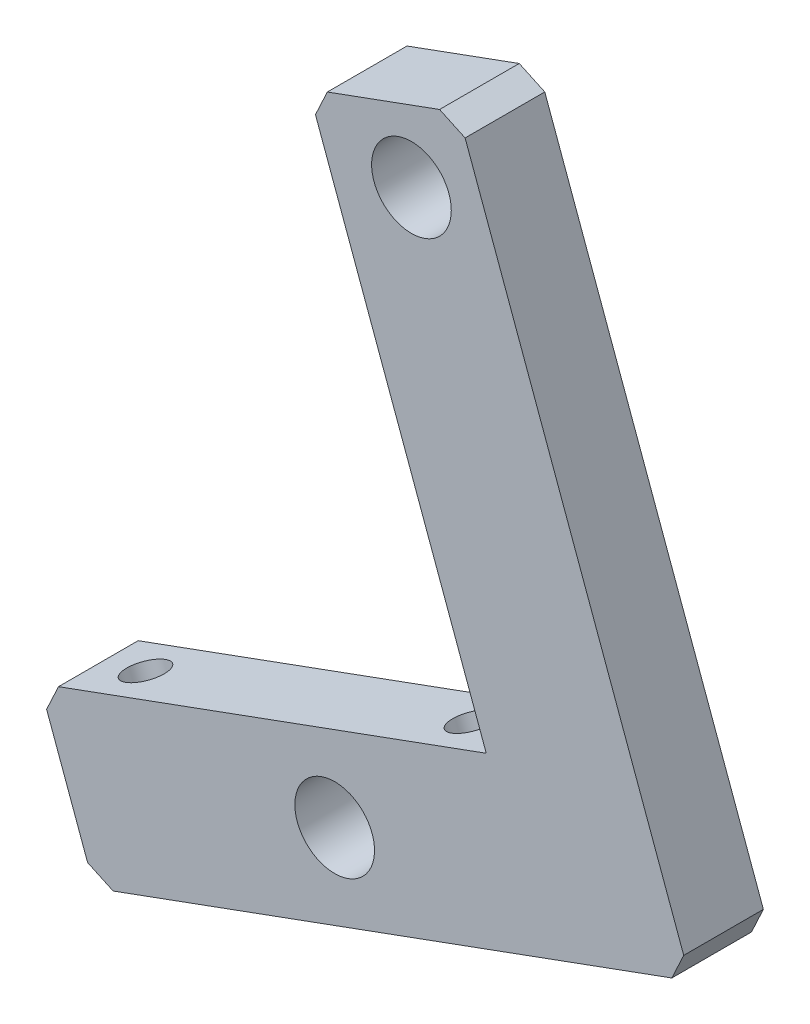
SolidWorks part; units mm, degrees
ref_plane "前基準面" through (0, 0, 0) normal (0, 0, 1) x (1, 0, 0)
ref_plane "上基準面" through (0, 0, 0) normal (0, 1, 0) x (1, 0, 0)
ref_plane "右基準面" through (0, 0, 0) normal (1, 0, 0) x (0, 0, -1)
sketch "草圖1" plane through (0, 0, 0) normal (0, 0, 1) x (1, 0, 0)
  line L0 (-29.9561, 9.7552) -> (-48.7426, 2.8947)
  line L2 (-48.7426, 2.8947) -> (-26.446, -58.1615)
  line L3 (-26.446, -58.1615) -> (-82.4902, -78.6278)
  line L4 (-82.4902, -78.6278) -> (-75.6297, -97.4144)
  line L5 (-75.6297, -97.4144) -> (-0.799, -70.0876)
  line L6 (-0.799, -70.0876) -> (-29.9561, 9.7552)
  circle A0 centre (-35.8357, -1.3461) radius 5
  dimension "D4" = 10
  dimension "D1" = 20
  dimension "D2" = 20
  dimension "D3" = 65
extrude "填料-伸長1" add sketch "草圖1" along normal blind 10
sketch "草圖2" plane through (15.6286, -42.7967, 0) normal (-0.343, 0.9393, 0) x (0.9393, 0.343, 0)
  circle A0 centre (-95.6715, -4.9822) radius 2.5
  circle A1 centre (-52.1263, -4.9822) radius 2.5
  dimension "D1" = 5
  dimension "D2" = 5
extrude "除料-伸長2" cut sketch "草圖2" against normal through all
chamfer "導角1" distance 2.5 angle 45 5 edges at (-29.9561, 9.7552, 5) (-48.7426, 2.8947, 5) (-0.799, -70.0876, 5) (-75.6297, -97.4144, 5) (-82.4902, -78.6278, 5)
sketch "草圖3" plane through (0, 0, 0) normal (0, 0, -1) x (-1, 0, 0)
  line L0 (152.0261, -114.667) -> (6.0939, -61.3752) construction
  circle A0 centre (45.4703, -75.7548) radius 5
  point P2 (0, 0)
  point P5 (79.06, -88.0211)
extrude "除料-伸長3" cut sketch "草圖3" against normal through all
